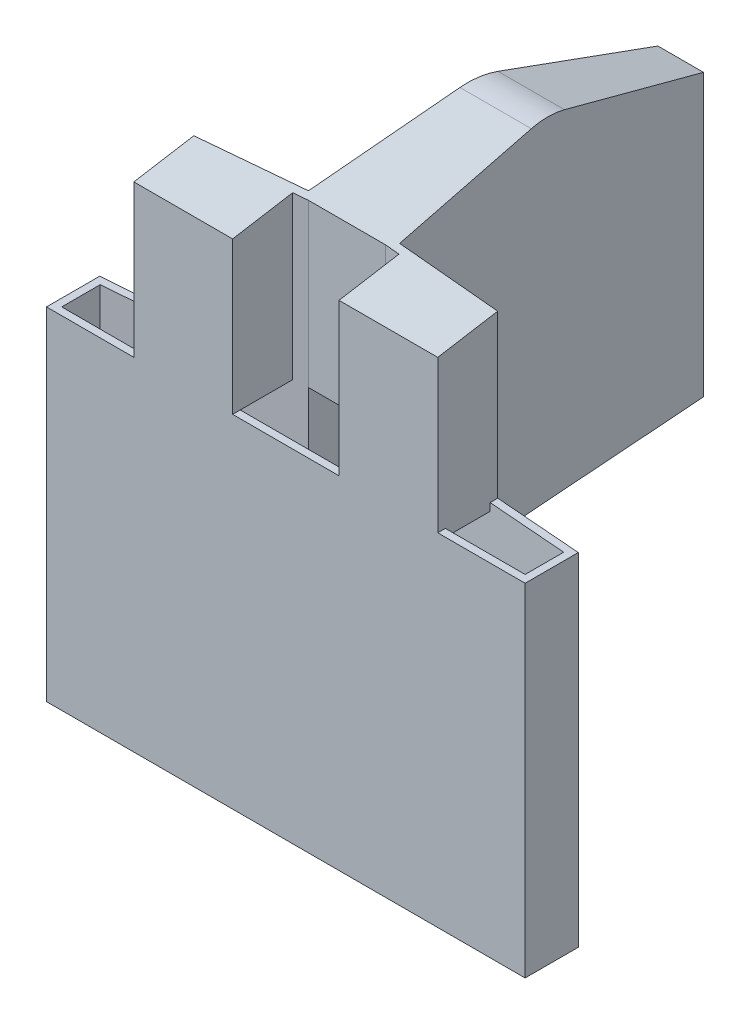
SolidWorks part; units mm, degrees
ref_plane "Front Plane" through (0, 0, 0) normal (0, 0, 1) x (1, 0, 0)
ref_plane "Top Plane" through (0, 0, 0) normal (0, 1, 0) x (1, 0, 0)
ref_plane "Right Plane" through (0, 0, 0) normal (1, 0, 0) x (0, 0, -1)
sketch "Sketch2" plane through (0, 0, 0) normal (0, 1, 0) x (1, 0, 0)
  line L0 (-18.9886, 28.3829) -> (-4.9886, 29.4702)
  line L1 (-30.4886, 20.4898) -> (32.5114, 20.4898)
  line L2 (-30.4886, 20.4898) -> (-30.4886, 27.4898)
  line L5 (-1.9886, 72.4702) -> (4.0114, 72.4702)
  line L10 (-1.9886, 72.4702) -> (-4.9886, 29.4702)
  line L17 (4.0114, 72.4702) -> (7.0114, 29.4702)
  line L22 (32.5114, 20.4898) -> (32.5114, 27.4898)
  line L23 (-30.4886, 27.4898) -> (-18.9886, 28.3829)
  line L25 (7.0114, 29.4702) -> (32.5114, 27.4898)
  dimension "D4" = 43
  dimension "D5" = 25.5
extrude "Boss-Extrude1" add sketch "Sketch2" along normal blind 70 contours L0 L10 L5 L17 L25 L22 L1 L2 L23
sketch "Sketch3" plane through (0, 70, 0) normal (0, 1, 0) x (1, 0, 0)
  line L1 (-30.4886, 27.4898) -> (-30.4886, 20.4898)
  line L2 (-30.4886, 20.4898) -> (-18.9886, 20.4898)
  line L3 (-30.4886, 20.4898) -> (32.5114, 20.4898) construction
  line L6 (21.0114, 20.4898) -> (32.5114, 20.4898)
  line L7 (32.5114, 20.4898) -> (32.5114, 27.4898)
  line L9 (-18.9886, 20.4898) -> (-18.9886, 28.3829)
  line L10 (-30.4886, 27.4898) -> (-4.9886, 29.4702) construction
  line L12 (21.0114, 20.4898) -> (21.0114, 28.3829)
  line L23 (-18.9886, 28.3829) -> (-30.4886, 27.4898)
  line L24 (21.0114, 28.3829) -> (32.5114, 27.4898)
  dimension "D1" = 40
extrude "Cut-Extrude1" cut sketch "Sketch3" against normal blind 25 contours L1 L2 L9 L23 | L6 L7 L24 L12
sketch "Sketch7" plane through (0, 0, 0) normal (1, 0, 0) x (0, 0, -1)
  line L0 (20.4898, 70) -> (20.4898, 65)
  line L1 (20.4898, 45) -> (20.4898, 70) construction
  line L2 (20.4898, 65) -> (50.4898, 70)
  line L3 (72.4702, 70) -> (29.4702, 70) construction
  line L4 (50.4898, 70) -> (20.4898, 70)
  line L5 (50.4898, 70) -> (72.4702, 70)
  line L6 (72.4702, 70) -> (72.4702, 63)
  line L7 (72.4702, 63) -> (50.4898, 70)
  dimension "D1" = 30
  dimension "D2" = 5
  dimension "D3" = 7
extrude "Cut-Extrude4" cut sketch "Sketch7" against normal blind 27 and the other way blind 24 contours L2 L4 L0 | L7 L6 L5 region at (0, 68.3333, -30.4898) region at (0, 67.6667, -65.1434)
shell "Shell2" thickness 1 removed face at (1.0114, 0, -37.48)
fillet "Fillet1" radius 10 1 edges at (1.0114, 70, -50.4898)
sketch "Sketch6" plane through (0, 0, 0) normal (0, -1, 0) x (1, 0, 0)
  line L0 (-4.9886, -29.4702) -> (7.0114, -29.4702)
  line L1 (7.0114, -29.4702) -> (4.0114, -72.4702)
  line L2 (4.0114, -72.4702) -> (-1.9886, -72.4702)
  line L3 (-1.9886, -72.4702) -> (-4.9886, -29.4702)
extrude "Cut-Extrude3" cut sketch "Sketch6" against normal blind 26
sketch "Sketch4" plane through (0, 45, 0) normal (0, 1, 0) x (1, 0, 0)
  line L0 (1.0114, 72.4702) -> (1.0114, 20.4898) construction
  line L7 (-18.9886, 28.3829) -> (-30.4886, 27.4898) construction
  line L8 (31.5114, 21.4898) -> (21.0114, 21.4898)
  line L9 (21.0114, 27.3799) -> (21.0114, 21.4898)
  line L19 (31.5114, 26.5644) -> (21.0114, 27.3799)
  line L23 (31.5114, 21.4898) -> (31.5114, 26.5644)
  line L36 (-29.4886, 21.4898) -> (-29.4886, 26.5644)
  line L37 (-29.4886, 26.5644) -> (-18.9886, 27.3799)
  line L38 (-18.9886, 20.4898) -> (-18.9886, 28.3829) construction
  line L39 (-18.9886, 27.3799) -> (-18.9886, 21.4898)
  line L42 (-29.4886, 21.4898) -> (-18.9886, 21.4898)
  line L43 (-30.4886, 20.4898) -> (-18.9886, 20.4898) construction
  line L44 (-30.4886, 27.4898) -> (-30.4886, 20.4898) construction
  dimension "D1" = 1
  dimension "D2" = 1
  dimension "D3" = 1
extrude "Cut-Extrude2" cut sketch "Sketch4" against normal blind 1
ref_plane "Plane1" through (0, 45, 0) normal (0, -1, 0) x (-1, 0, 0)
sketch "Sketch16" plane through (0, 45, 0) normal (0, -1, 0) x (-1, 0, 0)
  line L0 (-6.009, 29.4702) -> (3.9861, 29.4702)
  line L1 (3.9861, 29.4702) -> (4.051, 28.54)
  line L2 (4.051, 28.54) -> (-6.0739, 28.54)
  line L3 (-6.0739, 28.54) -> (-6.009, 29.4702)
extrude "Boss-Extrude4" add sketch "Sketch16" against normal blind 21.5
sketch "Sketch19" plane through (0, 45, 0) normal (0, -1, 0) x (-1, 0, 0)
  line L0 (5.9886, 28.3896) -> (5.9886, 21.4898)
  line L1 (17.9886, 27.4576) -> (4.051, 28.54) construction
  line L2 (5.9886, 28.3896) -> (6.9886, 28.3119)
  line L3 (29.4886, 26.5644) -> (4.051, 28.54) construction
  line L4 (6.9886, 28.3119) -> (6.9886, 21.4898)
  line L5 (29.4886, 21.4898) -> (-31.5114, 21.4898) construction
  line L6 (6.9886, 21.4898) -> (5.9886, 21.4898)
  line L7 (-8.0114, 21.4898) -> (-8.0114, 28.3896)
  line L8 (-6.0739, 28.54) -> (-31.5114, 26.5644) construction
  line L9 (-8.0114, 28.3896) -> (-9.0114, 28.3119)
  line L10 (-9.0114, 28.3119) -> (-9.0114, 21.4898)
  line L11 (-20.0114, 21.4898) -> (17.9886, 21.4898) construction
  line L12 (-9.0114, 21.4898) -> (-8.0114, 21.4898)
  dimension "D1" = 1
  dimension "D2" = 1
extrude "Boss-Extrude5" add sketch "Sketch19" against normal blind 22
sketch "Sketch20" plane through (-5.9886, 0, 0) normal (1, 0, 0) x (0, 0, -1)
  line L0 (21.4898, 67) -> (21.4898, 65.1667)
  line L1 (28.3829, 66.3155) -> (20.4898, 65) construction
  line L2 (21.4898, 65.1667) -> (28.3119, 66.3037) construction
  line L9 (21.4898, 67) -> (30.6098, 67)
  line L10 (30.6098, 67) -> (30.6098, 66.6867)
  line L11 (48.1101, 69.6034) -> (29.4702, 66.4967) construction
  line L12 (30.6098, 66.6867) -> (21.4898, 65.1667)
extrude "Cut-Extrude8" cut sketch "Sketch20" against normal mid plane 40
sketch "Sketch22" plane through (0, 45, 0) normal (0, -1, 0) x (-1, 0, 0)
  line L0 (-8.0114, 28.3896) -> (-8.0114, 20.4898)
  line L1 (30.4886, 20.4898) -> (-32.5114, 20.4898) construction
  line L2 (5.9886, 28.3896) -> (5.9886, 20.4898)
  line L3 (5.9886, 20.4898) -> (-8.0114, 20.4898)
  line L4 (-8.0114, 28.3896) -> (-6.0739, 28.54)
  line L5 (-6.0739, 28.54) -> (4.051, 28.54)
  line L6 (4.051, 28.54) -> (5.9886, 28.3896)
extrude "Cut-Extrude10" cut sketch "Sketch22" against normal blind 34
